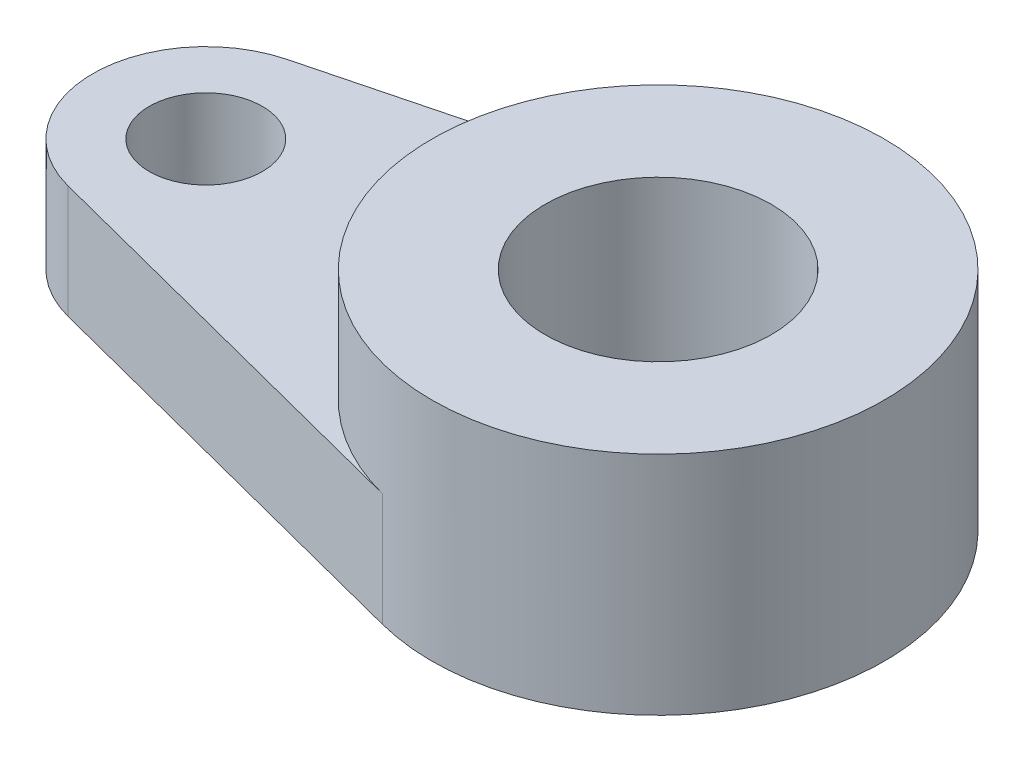
SolidWorks part; units mm, degrees
ref_plane "Front Plane" through (0, 0, 0) normal (0, 0, 1) x (1, 0, 0)
ref_plane "Top Plane" through (0, 0, 0) normal (0, 1, 0) x (1, 0, 0)
ref_plane "Right Plane" through (0, 0, 0) normal (1, 0, 0) x (0, 0, -1)
sketch "Sketch1" plane through (0, 0, 0) normal (0, 1, 0) x (1, 0, 0)
  line L0 (-12.75, 2.9047) -> (-1.5, 5.8095)
  line L1 (-12.75, -2.9047) -> (-1.5, -5.8095)
  circle A0 centre (0, 0) radius 6
  circle A1 centre (-12, 0) radius 3
  dimension "D1" = 12
  dimension "D2" = 6
  dimension "D3" = 21
extrude "Boss-Extrude1" add sketch "Sketch1" along normal blind 6 contours A0 region at (0, 0, 0)
extrude "Boss-Extrude2" add sketch "Sketch1<3>" along normal blind 3 contours A1 L1 A0 L0 | A1 region at (-7.3642, 0, 0) region at (-12, 0, 0)
sketch "Sketch1<3>" plane through (0, 0, 0) normal (0, 1, 0) x (1, 0, 0) same geometry as "Sketch1"
sketch "Sketch2" plane through (0, 6, 0) normal (0, -1, 0) x (1, 0, 0)
  circle A0 centre (0, 0) radius 3
  circle A1 centre (-12, 0) radius 1.5
  arc A2 (-12.75, 2.9047) -> (-12.75, -2.9047) centre (-12, 0) ccw construction
  dimension "D1" = 6
  dimension "D2" = 3
extrude "Cut-Extrude1" cut sketch "Sketch2" along normal through all
